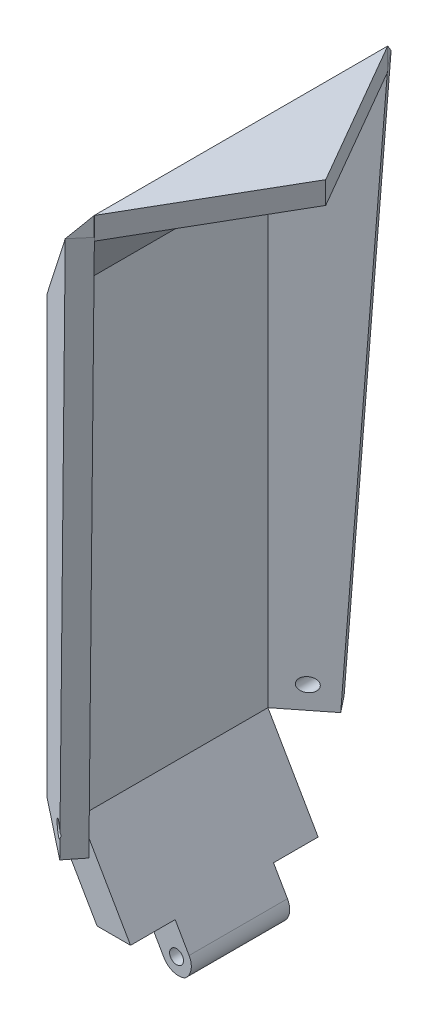
SolidWorks part; units mm, degrees
ref_plane "Front Plane" through (0, 0, 0) normal (0, 0, 1) x (1, 0, 0)
ref_plane "Top Plane" through (0, 0, 0) normal (0, 1, 0) x (1, 0, 0)
ref_plane "Right Plane" through (0, 0, 0) normal (1, 0, 0) x (0, 0, -1)
sketch "Sketch1" plane through (0, 0, 0) normal (0, 1, 0) x (1, 0, 0)
  line L4 (0, 0) -> (0, 16.82)
  line L5 (0, 16.82) -> (7.8551, 23.0085)
  line L6 (7.8551, 23.0085) -> (9.004, 21.5502)
  line L7 (9.004, 21.5502) -> (3, 16.82)
  line L8 (3, 16.82) -> (3, 0)
  line L9 (3, 0) -> (8.9971, -4.739)
  line L10 (8.9971, -4.739) -> (7.846, -6.2)
  line L11 (7.846, -6.2) -> (0, 0)
  dimension "D1" = 16.82
  dimension "D2" = 10
  dimension "D3" = 10
  dimension "D4" = 3
  dimension "D5" = 1.86
  dimension "D6" = 1.8566
extrude "Boss-Extrude1" add sketch "Sketch1" along normal blind 50
sketch "Sketch8" plane through (0, 0, 0) normal (0, 0, 1) x (1, 0, 0)
  line L0 (0, 0) -> (5.9985, -10.3896) construction
  line L2 (0, 50) -> (0, 0) construction
  line L3 (3, 0) -> (7, 0) construction
  dimension "D1" = 150
  dimension "3.5" = 4
sketch "Sketch2" plane through (0, 0, 0) normal (-0.62, 0, 0.7846) x (0.7846, 0, 0.62)
  line L0 (11.46, 50) -> (0, 37)
  line L1 (0, 50) -> (0, 0) construction
  line L2 (0, 37) -> (0, 50)
  line L3 (0, 50) -> (11.46, 50)
  dimension "D1" = 13
  dimension "D2" = 11.46
extrude "Cut-Extrude1" cut sketch "Sketch2" along direction (0, 0, 1) on the side against the normal blind 30
sketch "Sketch5" plane through (-17.3103, 11.9728, 0) normal (-0.8224, 0.5688, 0) x (0, 0, 1)
  line L0 (0, 30.4304) -> (6.2, 44.2232)
  line L1 (6.2, 44.2232) -> (4.746, 46.2369)
  line L5 (-21.566, 46.2369) -> (-23.0085, 44.2391)
  line L6 (-23.0085, 44.2391) -> (-16.82, 30.4304)
  line L7 (-16.82, 30.4304) -> (0, 30.4304)
  line L8 (-21.566, 46.2369) -> (4.746, 46.2369)
extrude "Boss-Extrude2" add sketch "Sketch5" along direction (0, -1, 0) on the side of the normal blind 2 contours L8 L1 L0 L7 L6 L5
sketch "Sketch6" plane through (0, 0, 0) normal (-0.62, 0, 0.7846) x (0.7846, 0, 0.62)
  line L0 (10, 50.3438) -> (7, 0)
  line L2 (7, 0) -> (10, 0)
  line L3 (10, 0) -> (10, 50.3438)
  dimension "D1" = 3
extrude "Cut-Extrude2" cut sketch "Sketch6" against normal blind 2
sketch "Sketch7" plane through (-8.1764, 0, -10.3783) normal (-0.6189, 0, -0.7855) x (-0.7855, 0, 0.6189)
  line L0 (-20.4091, 50.3569) -> (-20.4091, 0)
  line L1 (-20.4091, 0) -> (-17.4091, 0)
  line L3 (-17.4091, 0) -> (-20.4091, 50.3569)
  dimension "D1" = 3
extrude "Cut-Extrude3" cut sketch "Sketch7" against normal blind 2
sketch "Sketch9" plane through (0, 0, 0) normal (0, -1, 0) x (1, 0, 0)
  line L0 (0, 0) -> (3, 0)
  line L1 (3, 0) -> (3, -16.82)
  line L2 (3, -16.82) -> (0, -16.82)
  line L3 (0, -16.82) -> (0, 0)
extrude "Boss-Extrude3" add sketch "Sketch9" along direction (0.5, -0.866, 0) on the side of the normal blind 13
sketch "Sketch10" plane through (0, 0, 0) normal (-0.866, -0.5, 0) x (0, 0, 1)
  line L0 (-16.82, -9) -> (-12.82, -9)
  line L1 (-16.82, -13) -> (-16.82, 0) construction
  line L2 (-12.82, -9) -> (-12.82, -13)
  line L3 (0, -13) -> (-16.82, -13) construction
  line L4 (-12.82, -13) -> (-16.82, -13)
  line L5 (-16.82, -13) -> (-16.82, -9)
  line L6 (0, -9) -> (-4, -9)
  line L7 (0, -13) -> (0, 0) construction
  line L8 (-4, -9) -> (-4, -13)
  line L9 (-4, -13) -> (0, -13)
  line L10 (0, -13) -> (0, -9)
  dimension "D1" = 4
  dimension "D2" = 4
  dimension "D3" = 4
extrude "Cut-Extrude4" cut sketch "Sketch10" along direction (1, 0, 0) on the side against the normal blind 15
sketch "Sketch11" plane through (0, 0, -12.82) normal (0, 0, -1) x (-1, 0, 0)
  line L4 (-9.5, -11.2583) -> (-7.25, -12.5574)
  line L5 (-7.25, -12.5574) -> (-6.5, -11.2583)
  line L6 (-6.5, -11.2583) -> (-9.5, -11.2583)
  line L8 (-9.5, -11.2583) -> (-7.5, -7.7942) construction
  line L9 (-6.5, -11.2583) -> (-4.5, -7.7942) construction
extrude "Boss-Extrude4" add sketch "Sketch11" against normal up to surface (8.82 mm away) contours L4 L5 L6 up to face at (7, -9.5263, -4)
fillet "Fillet1" radius 1.5 2 edges at (9.5, -11.2583, -8.41) (7.25, -12.5574, -8.41)
sketch "Sketch12" plane through (0, 0, -4) normal (0, 0, 1) x (1, 0, 0)
  line L0 (8.75, -9.9593) -> (6.5, -11.2583) construction
  circle A0 centre (7.625, -10.6088) radius 0.625
  point P8 (7.625, -10.6088)
  dimension "D1" = 1.25
extrude "Cut-Extrude5" cut sketch "Sketch12" against normal through all
sketch "Sketch15" plane through (0, 0, 0) normal (0, 0, 1) x (1, 0, 0)
  line L0 (3, 0) -> (7, 0) construction
  circle A0 centre (5, 2) radius 0.625
  point P5 (5, 0)
  dimension "D1" = 1.25
  dimension "D2" = 2
  dimension "D3" = 2
extrude "Cut-Extrude7" cut sketch "Sketch15" against normal through all and the other way through all
sketch "Sketch17" plane through (8.9915, 0, 0) normal (1, 0, 0) x (0, 0, -1)
  line L0 (-4.746, 52) -> (-4.7173, 50)
  line L1 (-4.7173, 50) -> (21.5317, 50)
  line L2 (21.5317, 50) -> (21.566, 52)
  line L3 (21.566, 52) -> (-4.746, 52)
extrude "Boss-Extrude5" add sketch "Sketch17" along normal blind 7.6
sketch "Sketch18" plane through (0, 52, 0) normal (0, 1, 0) x (1, 0, 0)
  line L0 (8.9915, 21.566) -> (16.5915, 8.41)
  line L1 (16.5915, 21.566) -> (16.5915, -4.746) construction
  line L4 (8.9915, 21.566) -> (16.5915, 21.566)
  line L5 (16.5915, 21.566) -> (16.5915, 8.41)
  point P10 (0, 0)
extrude "Cut-Extrude8" cut sketch "Sketch18" against normal blind 3
sketch "Sketch19" plane through (0, 52, 0) normal (0, 1, 0) x (1, 0, 0)
  line L0 (16.5915, 8.41) -> (8.9915, -4.746)
  line L1 (8.9915, -4.746) -> (16.5915, -4.746)
  line L2 (16.5915, -4.746) -> (16.5915, 8.41)
extrude "Cut-Extrude9" cut sketch "Sketch19" against normal blind 3
equation "\"8.5.000000mm\"=9"
